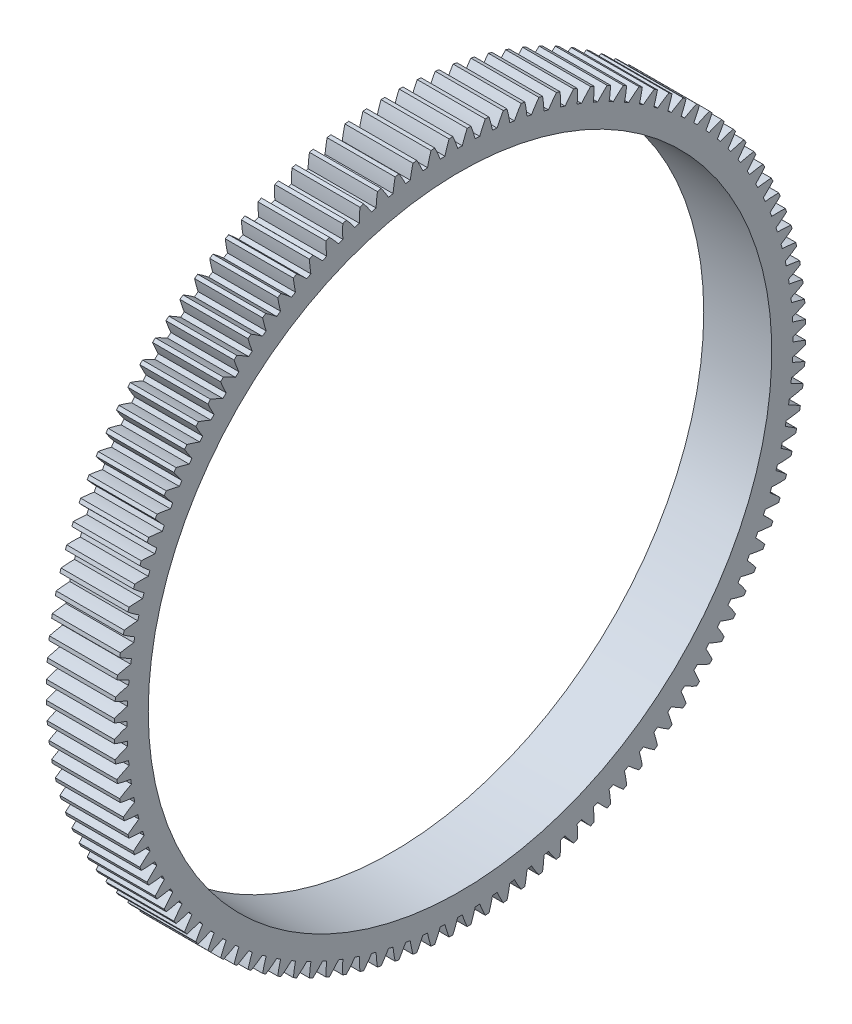
SolidWorks part; units mm, degrees
ref_plane "Plane1" through (0, 0, 0) normal (0, 0, 1) x (1, 0, 0)
ref_plane "Plane2" through (0, 0, 0) normal (0, 1, 0) x (1, 0, 0)
ref_plane "Plane3" through (0, 0, 0) normal (1, 0, 0) x (0, 0, -1)
other "Configuration Table"
sketch "HoldingSke" plane through (0, 0, 0) normal (0, 1, 0) x (1, 0, 0)
  line L0 (0, 0) -> (-0.5, -0.866)
  line L1 (-15, 0) -> (100, 0) construction
  line L2 (0, 0) -> (-2.1039, 2.3779)
  line L3 (0, 0) -> (-11.863, 4.5341)
  line L4 (0, 0) -> (-4.318, 7.479)
  line L5 (0, 0) -> (-46.8476, -17.4728)
  line L6 (0, 0) -> (-9.9476, -6.7116)
  line L7 (-2.1039, 2.3779) -> (8.6586, 51.2059)
  line L8 (-76.2, 54.61) -> (-68.8, 54.61)
  line L9 (-71.009, 38.7566) -> (-53.1078, 45.2721)
  line L10 (-76.2, 71.12) -> (104.1128, 71.12)
  line L11 (0, 0) -> (-12, 0)
  line L12 (-76.2, 101.6) -> (-76.162, 101.6)
  line L13 (24.9733, 27.94) -> (52.9518, 28.4284)
  line L14 (24.9733, 27.94) -> (24.9743, 27.94)
  line L15 (24.9733, 27.94) -> (100.4006, 29.5858)
  line L16 (-63.627, -1) -> (-12.827, -1)
  circle A0 centre (0, 0) radius 55
  circle A1 centre (0, 0) radius 37.5
  circle A2 centre (0, 0) radius 37.5
  circle A3 centre (0, 0) radius 55
  dimension "Num_teeth" = 120
  dimension "Pitch_radius" = 180.3128
  dimension "Width" = 12
  dimension "Thickness" = 12
sketch "BasProSke" plane through (0, 0, 0) normal (0, 1, 0) x (1, 0, 0)
  line L0 (-10, 0) -> (60, 0) construction
  line L1 (0, 0) -> (0, 61)
  line L2 (0, 0) -> (12, 0)
  line L3 (12, 0) -> (12, 61)
  line L4 (12, 61) -> (0, 61)
  dimension "Thickness" = 12
  dimension "Diameter" = 122
revolve "Base-Revolve" add sketch "BasProSke" angle 360 about L0
sketch "TooCutSke" plane through (0, 0, 0) normal (1, 0, 0) x (0, 0, -1)
  line L1 (0, 0) -> (0, 107) construction
  line L2 (0, 0) -> (-0.8519, 59.994) construction
  line L3 (0, 0) -> (-3.141, 119.9503) construction
  line L4 (-0.8519, 59.994) -> (-1.5705, 59.9751) construction
  arc A0 (0.4107, 58.7476) -> (-0.4107, 58.7476) centre (0, 0) ccw
  arc A1 (1.2712, 61.0122) -> (-1.2712, 61.0122) centre (0, 0) ccw
  circle A2 centre (0, 0) radius 60 construction
  circle A3 centre (0, 0) radius 56.3816 construction
  arc A4 (-0.4107, 58.7476) -> (-1.2712, 61.0122) centre (-23.2473, 51.3658) ccw
  arc A5 (1.2712, 61.0122) -> (0.4107, 58.7476) centre (23.2473, 51.3658) ccw
extrude "ToothCut" cut sketch "TooCutSke" along normal through all
fillet "Breaks" [suppressed] radius 0.02 tangent propagation no
fillet "RootFillets" [suppressed] radius 0.251
pattern_circular "TeethCuts" count 120 every 3 about axis through (-10, 0, 0) along (1, 0, 0) of "ToothCut", "RootFillets", "Breaks"
sketch "HubNeaOneSke" plane through (0, 0, 0) normal (-1, 0, 0) x (0, 0, 1)
  circle A0 centre (0, 0) radius 37.5
  dimension "Diameter" = 75
extrude "HubNearOne" [suppressed] add sketch "HubNeaOneSke" along normal blind 38.0001
sketch "HubNeaBotSke" plane through (0, 0, 0) normal (-1, 0, 0) x (0, 0, 1)
  circle A0 centre (0, 0) radius 37.5
  dimension "Diameter" = 75
extrude "HubNearBoth" [suppressed] add sketch "HubNeaBotSke" along normal blind 19
ref_plane "FarPln" through (12, 0, 0) normal (1, 0, 0) x (0, 0, -1)
sketch "HubFarSke" plane through (12, 0, 0) normal (1, 0, 0) x (0, 0, -1)
  circle A0 centre (0, 0) radius 37.5
  dimension "Diameter" = 75
extrude "HubFar" [suppressed] add sketch "HubFarSke" along normal blind 19
sketch "BorSke" plane through (0, 0, 0) normal (1, 0, 0) x (0, 0, -1)
  circle A0 centre (0, 0) radius 55
  dimension "Diameter" = 110
extrude "Bore" cut sketch "BorSke" along normal mid plane 100.0001
sketch "KeySke" plane through (0, 0, 0) normal (1, 0, 0) x (0, 0, -1)
  line L0 (-16, 0) -> (-16, 62.4)
  line L1 (-16, 62.4) -> (16, 62.4)
  line L2 (16, 62.4) -> (16, 0)
  line L3 (0, 0) -> (0, 34) construction
  line L4 (-16, 0) -> (16, 0)
  dimension "Width" = 32
extrude "Keyway" [suppressed] cut sketch "KeySke" along normal mid plane 100.0001
pattern_circular "Keyway2" [suppressed] count 2 every 90 about axis through (-10, 0, 0) along (1, 0, 0) reverse direction yes
equation "' \"Module@HoldingSke\" = 6.35"
equation "' \"Num_teeth@HoldingSke\" = 12"
equation "' \"Ap@HoldingSke\" =  20"
equation "' \"Ap@HoldingSke\" = 20"
equation "' \"Width@HoldingSke\" = 0.5 * 25.4"
equation "' \"Hub_dia@HoldingSke\"= 1 * 25.4"
equation "' \"Hub_dia@HoldingSke\" = 1 * 25.4"
equation "' \"Overall_len@HoldingSke\" = 1.0 * 25.4"
equation "' \"Bore@HoldingSke\" = 0.75 * 25.4"
equation "' \"T_dim@HoldingSke\" = 0.1 * 25.4"
equation "' \"Width@KeySke\" = 0.25 * 25.4"
equation "' \"Show_teeth@HoldingSke\" = 13"
equation "' \"Backlash@HoldingSke\" = 0.009 * 25.4"
equation "' \"Addendum_fac@HoldingSke\" = 1.0"
equation "' \"Dedendum_fac@HoldingSke\" = 1.25"
equation "' \"Dedendum_add@HoldingSke\" = 0.00005 * 25.4"
equation "' \"Clearance_fac@HoldingSke\" = 0.25"
equation "\"Pitch@HoldingSke\" = 1 / \"Module@HoldingSke\""
equation "\"Overcut_dia@TooCutSke\" = (\"Num_teeth@HoldingSke\" + 2 * \"Addendum_fac@HoldingSke\") / \"Pitch@HoldingSke\" + 0.002 * 25.4"
equation "\"Pitch_dia@TooCutSke\" = \"Num_teeth@HoldingSke\" / \"Pitch@HoldingSke\""
equation "\"Base_dia@TooCutSke\" = \"Num_teeth@HoldingSke\" / \"Pitch@HoldingSke\" * cos((\"Ap@HoldingSke\"  * 3.14159265 / 180))"
equation "\"Root_dia@TooCutSke\" = (\"Num_teeth@HoldingSke\" + 2) / \"Pitch@HoldingSke\" - 2 * (\"Addendum_fac@HoldingSke\" + \"Dedendum_fac@HoldingSke\") / \"Pitch@HoldingSke\" - \"Dedendum_add@HoldingSke\" * 2"
equation "\"Half_ang@TooCutSke\" = 180 / \"Num_teeth@HoldingSke\""
equation "\"Half_CT@TooCutSke\" = \"Num_teeth@HoldingSke\" / \"Pitch@HoldingSke\" * sin((3.14159265 / 2 / \"Num_teeth@HoldingSke\")) / 2 - 7 * \"Backlash@HoldingSke\" / 4"
equation "\"Flank_rad@TooCutSke\" = \"Num_teeth@HoldingSke\" / \"Pitch@HoldingSke\" / 5"
equation "\"Radius@RootFillets\" = \"Clearance_fac@HoldingSke\" / \"Pitch@HoldingSke\" + \"Dedendum_add@HoldingSke\""
equation "\"Break_rad@Breaks\" = 0.02 / \"Pitch@HoldingSke\""
equation "\"Thickness@HoldingSke\" = \"Width@HoldingSke\""
equation "\"OAL@HoldingSke\" = \"Thickness@HoldingSke\""
equation "\"MHD@HoldingSke\" = (\"Num_teeth@HoldingSke\" + 2) / \"Pitch@HoldingSke\" - 2 * (\"Addendum_fac@HoldingSke\" + \"Dedendum_fac@HoldingSke\")  / \"Pitch@HoldingSke\" - \"Dedendum_add@HoldingSke\" * 2"
equation "\"MBD@HoldingSke\" = (\"Num_teeth@HoldingSke\" + 2) / \"Pitch@HoldingSke\" - 2 * (\"Addendum_fac@HoldingSke\" + \"Dedendum_fac@HoldingSke\")  / \"Pitch@HoldingSke\" - \"Dedendum_add@HoldingSke\" * 2 - 0.002 * 25.4"
equation "\"MHD@HoldingSke\" = ((sgn( \"MHD@HoldingSke\" - \"Hub_dia@HoldingSke\" )-1)*( \"MHD@HoldingSke\" - \"Hub_dia@HoldingSke\" ))/-2+ \"Hub_dia@HoldingSke\""
equation "\"MBD@HoldingSke\" = ((sgn( \"MBD@HoldingSke\" - \"Bore@HoldingSke\" )-1)*( \"MBD@HoldingSke\" - \"Bore@HoldingSke\" ))/-2+ \"Bore@HoldingSke\""
equation "\"OAL@HoldingSke\" = ((sgn( \"OAL@HoldingSke\" - \"Overall_len@HoldingSke\" )+1)*( \"OAL@HoldingSke\" - \"Overall_len@HoldingSke\" ))/2 + \"Overall_len@HoldingSke\" + 0.000002 * 25.4"
equation "\"Num_teeth@TeethCuts\" = int( \"Show_teeth@HoldingSke\" ) + 1"
equation "\"Num_teeth@TeethCuts\" = ((sgn( \"Num_teeth@TeethCuts\" - \"Num_teeth@HoldingSke\" )-1)*( \"Num_teeth@TeethCuts\" - \"Num_teeth@HoldingSke\" ))/-2+ \"Num_teeth@HoldingSke\""
equation "\"Num_teeth@TeethCuts\" = ((sgn( \"Num_teeth@TeethCuts\" - 2.0)+1)*( \"Num_teeth@TeethCuts\" - 2.0))/2 +2.0"
equation "\"Angle@TeethCuts\" = 360.0 / \"Num_teeth@HoldingSke\""
equation "\"Diameter@BasProSke\" = (\"Num_teeth@HoldingSke\" + 2 * \"Addendum_fac@HoldingSke\") / \"Pitch@HoldingSke\""
equation "\"Thickness@BasProSke\"  = \"Thickness@HoldingSke\""
equation "' \"Fillet_rad@BasProSke\" =  \"Thickness@HoldingSke\" * 0.05"
equation "' \"Fillet_rad@BasProSke\" = \"Thickness@HoldingSke\" * 0.05"
equation "\"MHD@HoldingSke\" = ((sgn( \"MHD@HoldingSke\" - \"Root_dia@TooCutSke\" )-1)*( \"MHD@HoldingSke\" - \"Root_dia@TooCutSke\" ))/-2+ \"Root_dia@TooCutSke\""
equation "\"Diameter@HubNeaOneSke\" = \"MHD@HoldingSke\""
equation "\"Length@HubNearOne\" = \"OAL@HoldingSke\" - \"Thickness@BasProSke\""
equation "\"Diameter@HubNeaBotSke\" = \"MHD@HoldingSke\""
equation "\"Length@HubNearBoth\" = ( \"OAL@HoldingSke\" - \"Thickness@BasProSke\" ) / 2.0"
equation "\"Thickness@FarPln\" = \"Thickness@BasProSke\""
equation "\"Diameter@HubFarSke\" = \"MHD@HoldingSke\""
equation "\"Length@HubFar\" = ( \"OAL@HoldingSke\" - \"Thickness@BasProSke\" ) / 2.0"
equation "\"Diameter@BorSke\" = \"MBD@HoldingSke\""
equation "\"D1@Bore\" = \"OAL@HoldingSke\" * 2.0"
equation "\"D1@Keyway\" = \"OAL@HoldingSke\" * 2.0"
equation "\"Offset@KeySke\" = \"T_dim@HoldingSke\" + \"MBD@HoldingSke\" / 2.0"
